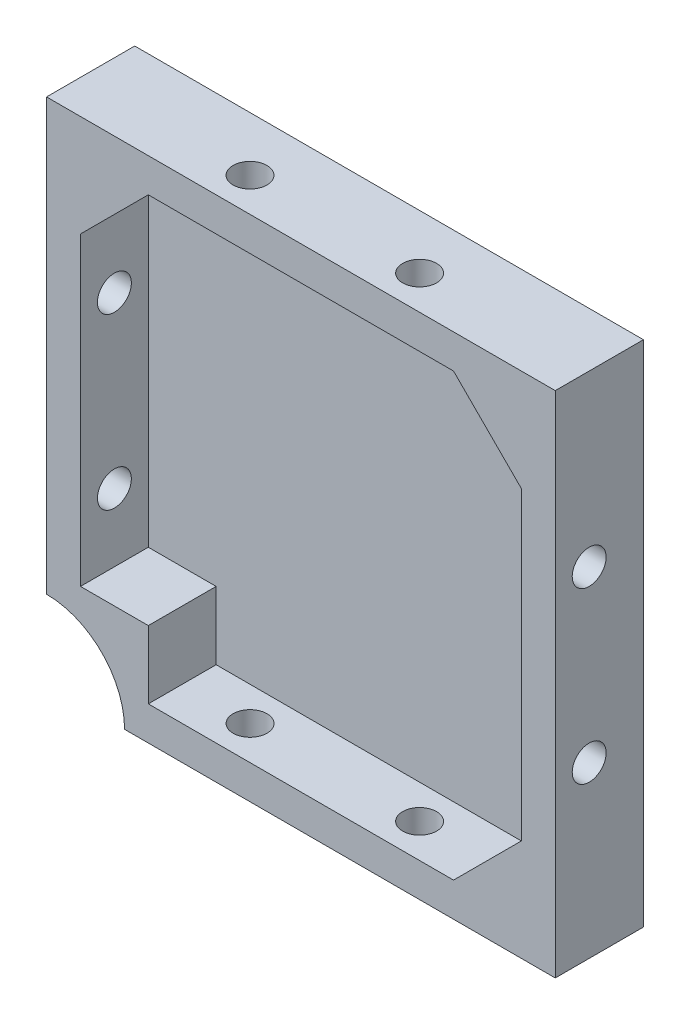
SolidWorks part; units mm, degrees
ref_plane "Plan de face" through (0, 0, 0) normal (0, 0, 1) x (1, 0, 0)
ref_plane "Plan de dessus" through (0, 0, 0) normal (0, 1, 0) x (1, 0, 0)
ref_plane "Plan de droite" through (0, 0, 0) normal (1, 0, 0) x (0, 0, -1)
sketch "Esquisse1" plane through (0, 0, 0) normal (0, 0, 1) x (1, 0, 0)
  line L0 (44.1184, 33.7284) -> (54.1184, 33.7284)
  line L1 (-20.8816, 33.7284) -> (44.1184, 33.7284)
  line L2 (-20.8816, 33.7284) -> (-20.8816, -41.2716)
  line L3 (-20.8816, -41.2716) -> (54.1184, -41.2716)
  line L4 (54.1184, 23.7284) -> (54.1184, -41.2716)
  line L5 (54.1184, 33.7284) -> (54.1184, 23.7284)
  point P6 (54.1184, 33.7284)
  dimension "D1" = 75
  dimension "D2" = 75
extrude "Boss.-Extru.1" add sketch "Esquisse1" along normal blind 13
shell "Coque1" thickness 5 removed face at (16.6184, -3.7716, 13)
sketch "Esquisse2" plane through (-20.8816, 0, 0) normal (-1, 0, 0) x (0, 0, 1)
  line L0 (13, 33.7284) -> (13, -41.2716) construction
  line L1 (13, 33.7284) -> (0, 33.7284) construction
  line L2 (13, -41.2716) -> (0, -41.2716) construction
  circle A0 centre (8, 8.7284) radius 2.5
  circle A1 centre (8, -16.2716) radius 2.5
  dimension "D1" = 5
  dimension "D2" = 5
  dimension "D3" = 5
  dimension "D4" = 5
  dimension "D5" = 25
  dimension "D6" = 25
extrude "Enlèv. mat.-Extru.1" cut sketch "Esquisse2" against normal up to surface (75 mm away) contours A1 | A0 region at (-20.8816, -16.2716, 8) up to face at (54.1184, -3.7716, 6.5)
sketch "Esquisse3" plane through (0, -41.2716, 0) normal (0, -1, 0) x (1, 0, 0)
  line L0 (-20.8816, 13) -> (54.1184, 13) construction
  line L2 (54.1184, 13) -> (54.1184, 0) construction
  line L3 (-20.8816, 13) -> (-20.8816, 0) construction
  circle A0 centre (4.1184, 8) radius 2.5
  circle A1 centre (29.1184, 8) radius 2.5
  dimension "D1" = 5
  dimension "D2" = 5
  dimension "D3" = 5
  dimension "D4" = 5
  dimension "D5" = 25
  dimension "D6" = 25
extrude "Enlèv. mat.-Extru.2" cut sketch "Esquisse3" against normal up to surface (75 mm away) up to face at (16.6184, 33.7284, 6.5)
sketch "Esquisse4" plane through (0, 0, 3) normal (0, 0, 1) x (1, 0, 0)
  line L0 (-5.8816, 28.7284) -> (-15.8816, 18.7284)
  line L1 (49.1184, 28.7284) -> (-15.8816, 28.7284) construction
  line L2 (-15.8816, 28.7284) -> (-15.8816, -36.2716) construction
  line L3 (-15.8816, 18.7284) -> (-15.8816, 28.7284)
  line L4 (-15.8816, 28.7284) -> (-5.8816, 28.7284)
  line L5 (49.1184, 28.7284) -> (49.1184, 18.7284)
  line L6 (49.1184, -36.2716) -> (49.1184, 28.7284) construction
  line L7 (49.1184, 18.7284) -> (39.1184, 28.7284)
  line L8 (39.1184, 28.7284) -> (49.1184, 28.7284)
  line L9 (49.1184, 28.7284) -> (-15.8816, 28.7284) construction
  line L10 (49.1184, -36.2716) -> (49.1184, -26.2716)
  line L11 (49.1184, -26.2716) -> (39.1184, -36.2716)
  line L12 (-15.8816, -36.2716) -> (49.1184, -36.2716) construction
  line L13 (39.1184, -36.2716) -> (49.1184, -36.2716)
  line L14 (-20.8816, -26.2716) -> (-5.8816, -26.2716)
  line L15 (-20.8816, -41.2716) -> (54.1184, -41.2716) construction
  line L16 (-5.8816, -26.2716) -> (-5.8816, -41.2716)
  line L17 (-5.8816, -41.2716) -> (-20.8816, -41.2716)
  line L18 (-20.8816, -41.2716) -> (-20.8816, -26.2716)
  line L19 (-20.8816, 33.7284) -> (-20.8816, -41.2716) construction
  dimension "D1" = 10
  dimension "D2" = 10
  dimension "D3" = 10
  dimension "D4" = 10
  dimension "D5" = 10
  dimension "D6" = 10
  dimension "D7" = 15
  dimension "D8" = 15
  dimension "D9" = 0
  dimension "D10" = 0
extrude "Boss.-Extru.2" add sketch "Esquisse4" along normal up to surface (10 mm away) up to face at (16.6184, -3.7716, 13)
sketch "Esquisse5" plane through (0, 0, 13) normal (0, 0, 1) x (1, 0, 0)
  circle A0 centre (-20.8816, -41.2716) radius 11.5
  dimension "D1" = 23
extrude "Enlèv. mat.-Extru.3" cut sketch "Esquisse5" against normal up to surface (13 mm away) up to face at (16.6184, -3.7716, 0)
